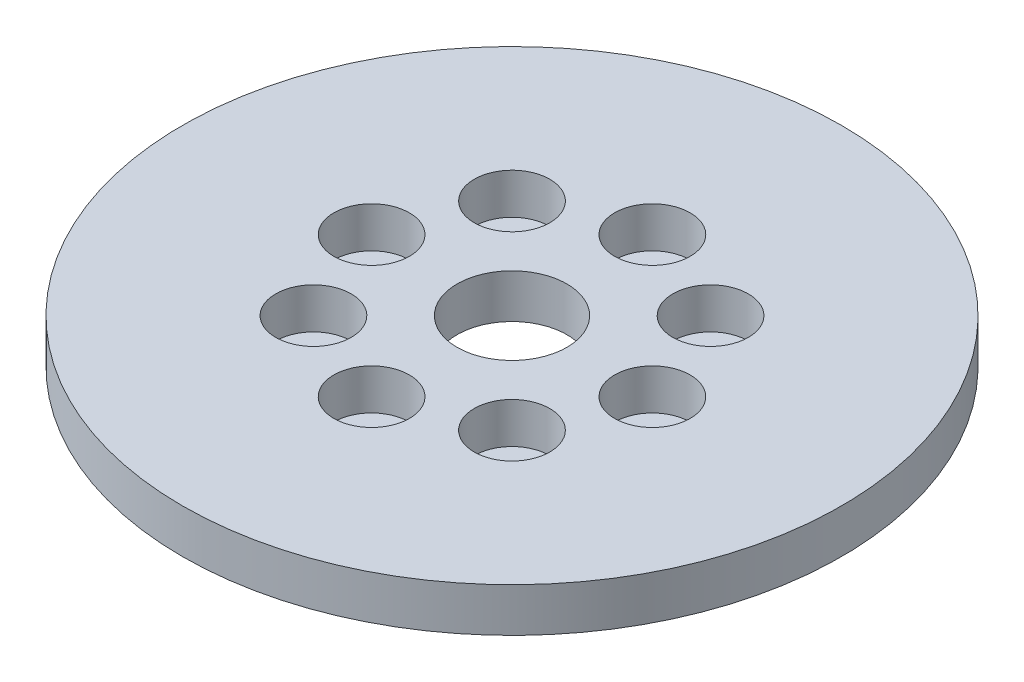
SolidWorks part; units mm, degrees
ref_plane "Front Plane" through (0, 0, 0) normal (0, 0, 1) x (1, 0, 0)
ref_plane "Top Plane" through (0, 0, 0) normal (0, 1, 0) x (1, 0, 0)
ref_plane "Right Plane" through (0, 0, 0) normal (1, 0, 0) x (0, 0, -1)
sketch "Sketch1" plane through (0, 0, 0) normal (0, 1, 0) x (1, 0, 0)
  circle A0 centre (0, 0) radius 45
  dimension "FLANGE_OD" = 90
extrude "Boss-Extrude1" add sketch "Sketch1" along normal blind 6
sketch "Sketch2" plane through (0, 0, 0) normal (0, 1, 0) x (1, 0, 0)
  circle A0 centre (0, 0) radius 7.5
  dimension "BORE_D" = 15
extrude "Cut-Extrude1" cut sketch "Sketch2" along normal through all
sketch "Sketch3" plane through (0, 6, 0) normal (0, 1, 0) x (1, 0, 0)
  circle A0 centre (0, 0) radius 19.1702 construction
  circle A1 centre (-19.1702, 0) radius 5.1556
  dimension "BOLT_D" = 10.3111
  dimension "BOLT_PCD" = 38.3403
extrude "Cut-Extrude2" cut sketch "Sketch3" against normal blind 5.5698
pattern_circular "CirPattern1" count 8 over 360 about axis through (0, 0, 0) along (0, 1, 0) of "Cut-Extrude2"
